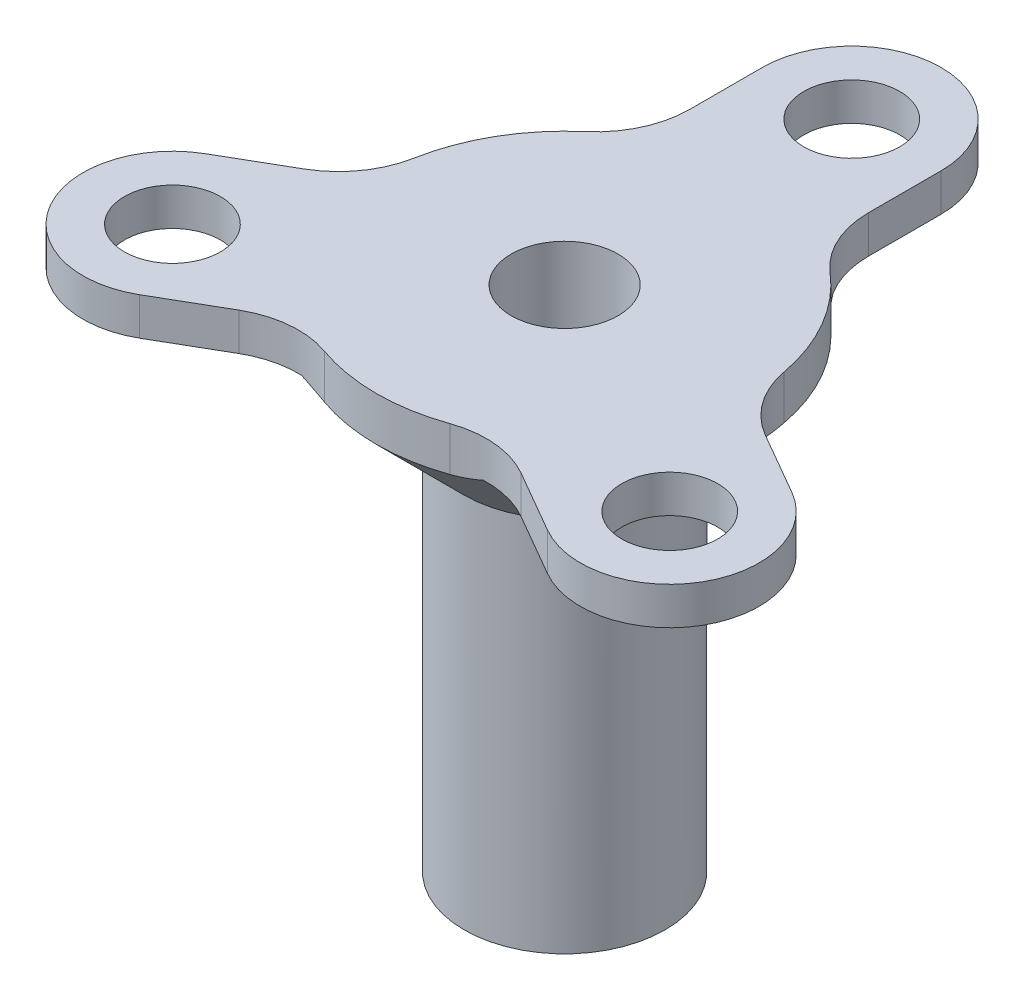
SolidWorks part; units mm, degrees
ref_plane "Front Plane" through (0, 0, 0) normal (0, 0, 1) x (1, 0, 0)
ref_plane "Top Plane" through (0, 0, 0) normal (0, 1, 0) x (1, 0, 0)
ref_plane "Right Plane" through (0, 0, 0) normal (1, 0, 0) x (0, 0, -1)
sketch "Sketch1" plane through (0, 0, 0) normal (0, 1, 0) x (1, 0, 0)
  circle A0 centre (0, 0) radius 10
  dimension "D1" = 20
extrude "Boss-Extrude1" add sketch "Sketch1" along normal blind 2
sketch "Sketch2" plane through (0, 2, 0) normal (0, 1, 0) x (1, 0, 0)
  line L0 (-4.75, 15.25) -> (-4.75, 8.7999)
  line L1 (4.75, 15.25) -> (4.75, 8.7999)
  circle A0 centre (0, 15.25) radius 2.55
  arc A1 (4.75, 15.25) -> (-4.75, 15.25) centre (0, 15.25) ccw
  circle A2 centre (0, 0) radius 10 construction
  arc A3 (-4.75, 8.7999) -> (4.75, 8.7999) centre (0, 0) cw
  dimension "D1" = 5.1
  dimension "D2" = 9.5
  dimension "D3" = 15.25
extrude "Boss-Extrude2" add sketch "Sketch2" against normal up to surface (2 mm away) up to face at (0, 0, 10)
pattern_circular "CirPattern1" count 3 over 360 about axis through (0, 2, 0) along (0, -1, 0) of "Boss-Extrude2"
sketch "Sketch3" plane through (0, 2, 0) normal (0, 1, 0) x (1, 0, 0)
  circle A0 centre (0, 0) radius 2.84
  dimension "D1" = 5.68
extrude "Cut-Extrude1" cut sketch "Sketch3" against normal through all
sketch "Sketch4" plane through (0, 0, 0) normal (0, -1, 0) x (1, 0, 0)
  circle A0 centre (0, 0) radius 2.84
  circle A1 centre (0, 0) radius 5.34
  circle A2 centre (0, 0) radius 2.84 construction
  dimension "D1" = 2.5
extrude "Boss-Extrude3" add sketch "Sketch4" along normal blind 25
sketch "Sketch7" plane through (0, -25, 0) normal (0, -1, 0) x (1, 0, 0)
  line L1 (-3.85, 0.55) -> (3.85, 0.55)
  line L2 (-3.85, 0.55) -> (-3.85, -0.55)
  line L3 (-3.85, -0.55) -> (3.85, -0.55)
  line L4 (3.85, 0.55) -> (3.85, -0.55)
  point P4 (-3.85, 0)
  point P6 (0, 0.55)
  dimension "D1" = 1.1
  dimension "D2" = 3.85
extrude "Cut-Extrude4" cut sketch "Sketch7" against normal blind 3
fillet "Fillet2" radius 5 6 edges at (-4.75, 1, -8.7999) (-9.9959, 1, 0.2863) (-5.2459, 1, 8.5135) (5.2459, 1, 8.5135) (9.9959, 1, 0.2863) (4.75, 1, -8.7999)
chamfer "Chamfer1" distance 5 angle 45 1 edges at (0, 0, 5.34)
